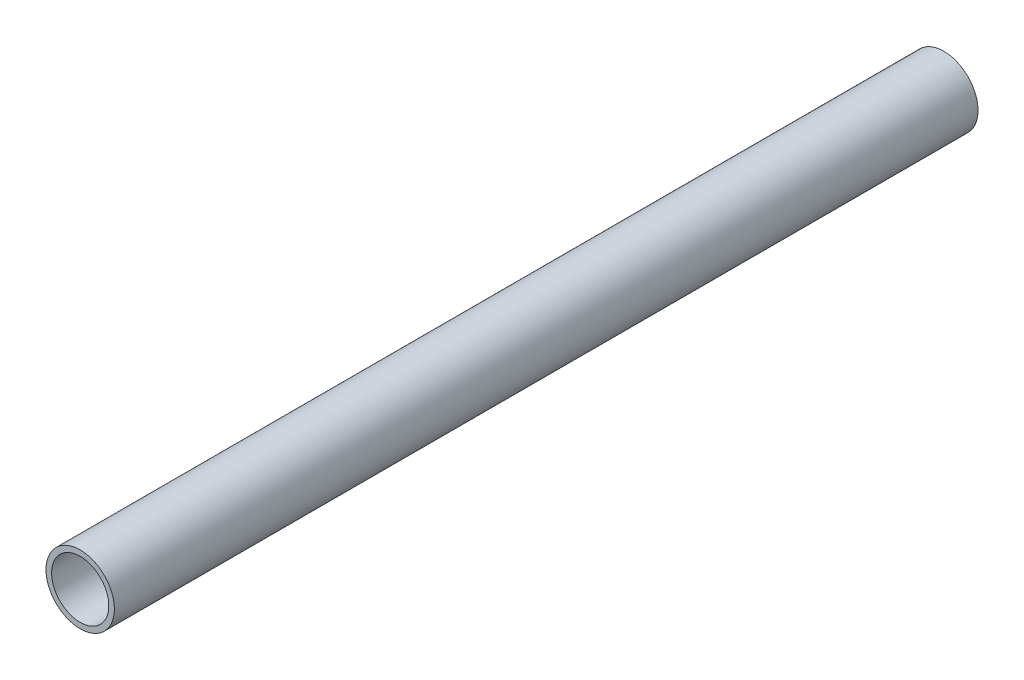
SolidWorks part; units mm, degrees
material "PVC Rigid"
ref_plane "Front Plane" through (0, 0, 0) normal (0, 0, 1) x (1, 0, 0)
ref_plane "Top Plane" through (0, 0, 0) normal (0, 1, 0) x (1, 0, 0)
ref_plane "Right Plane" through (0, 0, 0) normal (1, 0, 0) x (0, 0, -1)
sketch "Sketch1" plane through (0, 0, 0) normal (0, 0, 1) x (1, 0, 0)
  circle A0 centre (0, 0) radius 20.193
  circle A1 centre (0, 0) radius 24.13
  dimension "D1" = 48.26
  dimension "D2" = 40.386
extrude "Boss-Extrude1" add sketch "Sketch1" along normal blind 609.6
ref_axis "Axis1" through (0, 0, 654.0881) along (0, 0, -1)
